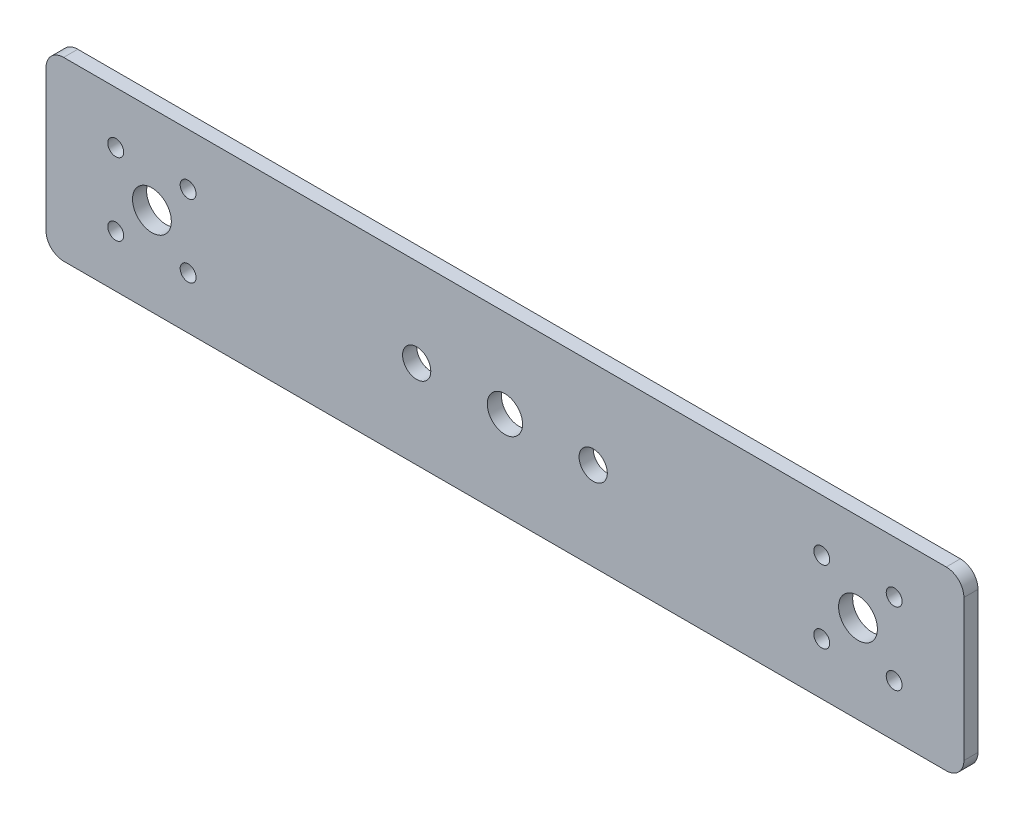
SolidWorks part; units mm, degrees
ref_plane "Front Plane" through (0, 0, 0) normal (0, 0, 1) x (1, 0, 0)
ref_plane "Top Plane" through (0, 0, 0) normal (0, 1, 0) x (1, 0, 0)
ref_plane "Right Plane" through (0, 0, 0) normal (1, 0, 0) x (0, 0, -1)
sketch "Sketch1" plane through (0, 0, 0) normal (0, 0, 1) x (1, 0, 0)
  line L1 (-130, -25) -> (130, -25)
  line L2 (-130, -25) -> (-130, 25)
  line L3 (-130, 25) -> (130, 25)
  line L4 (130, -25) -> (130, 25)
  line L5 (-130, -25) -> (130, 25) construction
  line L6 (-130, 25) -> (130, -25) construction
  point P0 (0, 0)
  dimension "D1" = 260
  dimension "D2" = 50
base flange "Base-Flange1" sketch "Sketch1" thickness 4 reverse thickness direction no parameters "D1"=0.7366
sketch "Sketch6" plane through (0, 0, 0) normal (0, 0, 1) x (1, 0, 0)
  line L0 (130, -25) -> (130, 25) construction
  line L1 (130, 25) -> (-130, 25) construction
  line L2 (100, 15) -> (100, -15) construction
  line L3 (115, 0) -> (85, 0) construction
  line L4 (0, 25) -> (0, -25) construction
  line L6 (0, 25) -> (0, -25) construction
  line L7 (-130, 0) -> (130, 0) construction
  line L8 (-130, 25) -> (-130, -25) construction
  circle A0 centre (100, 0) radius 5.5
  circle A1 centre (-100, 0) radius 5.5
  circle A2 centre (0, 0) radius 5
  circle A3 centre (-25, 0) radius 4
  circle A4 centre (25, 0) radius 4
  circle A5 centre (110.253, 10.253) radius 2.25
  circle A6 centre (89.747, 10.253) radius 2.25
  circle A7 centre (89.747, -10.253) radius 2.25
  circle A8 centre (110.253, -10.253) radius 2.25
  circle A9 centre (-110.253, -10.253) radius 2.25
  circle A10 centre (-89.747, -10.253) radius 2.25
  circle A11 centre (-89.747, 10.253) radius 2.25
  circle A12 centre (-110.253, 10.253) radius 2.25
  dimension "D2" = 11
  dimension "D3" = 30
  dimension "D4" = 105
  dimension "D5" = 130
  dimension "D6" = 155
  dimension "D7" = 230
  dimension "D9" = 4.5
  dimension "D10" = 89.747
  dimension "D11" = 20.5061
  dimension "D12" = 10
  dimension "D13" = 8
  dimension "D14" = 8
  dimension "D8" = 25
extrude "Cut-Extrude1" cut sketch "Sketch6" against normal blind 10 normal cut yes
fillet "Fillet1" radius 5 4 edges at (-130, -25, -2) (130, -25, -2) (130, 25, -2) (-130, 25, -2)
sketch "Bend-Lines1" [suppressed] plane through (0, 0, 0) normal (0, 1, 0) x (1, 0, 0)
sketch "Bounding-Box1" [suppressed] plane through (0, 0, 0) normal (0, 1, 0) x (1, 0, 0)
sheet metal parameters "Sheet-Metal1" thickness 4 parameters "D1"=0.7366
flat pattern "Flat-Pattern1" [suppressed]
sketch "Bend-Lines2" plane through (0, 0, 0) normal (0, 1, 0) x (1, 0, 0)
sketch3d "Bounding-Box2" [suppressed]
  line L0 (115, -25, 0) -> (-115, -25, 0) construction
  line L1 (115, 25, 0) -> (-115, 25, 0) construction
  line L2 (115, -25, 0) -> (115, 25, 0) construction
  line L3 (-115, -25, 0) -> (-115, 25, 0) construction
sheet metal parameters "Sheet-Metal2" thickness 4 parameters "D1"=0.7366
flat pattern "Flat-Pattern1"
sketch "Bend-Lines2" plane through (0, 0, 0) normal (0, 1, 0) x (1, 0, 0)
sketch3d "Bounding-Box2" [suppressed]
  line L0 (-130, 25, 0) -> (130, 25, 0) construction
  line L1 (-130, -25, 0) -> (130, -25, 0) construction
  line L2 (-130, 25, 0) -> (-130, -25, 0) construction
  line L3 (130, 25, 0) -> (130, -25, 0) construction
